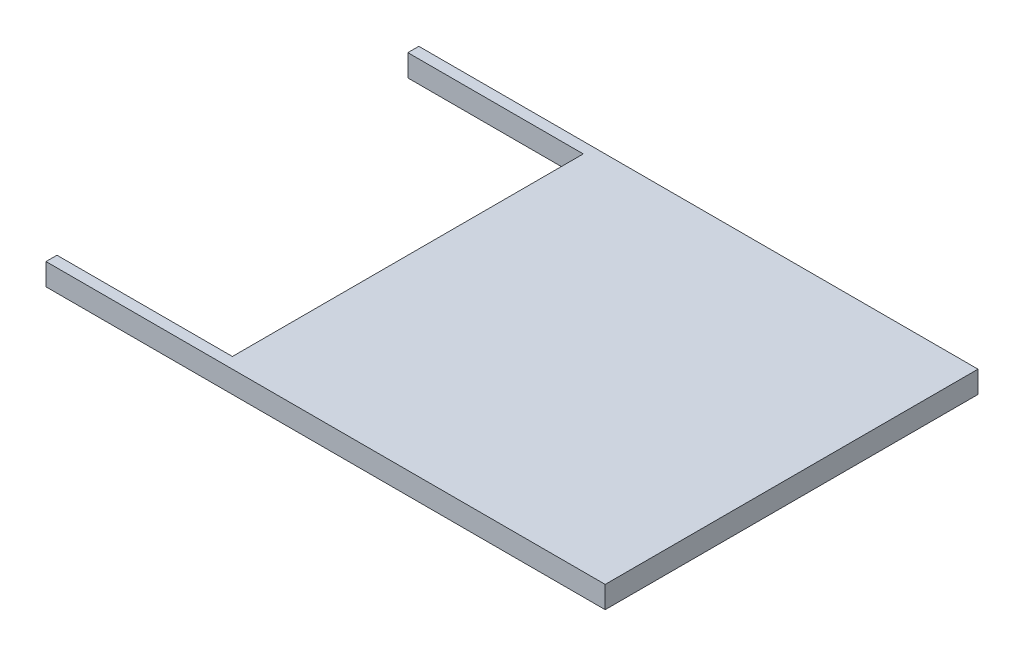
SolidWorks part; units mm, degrees
ref_plane "Front Plane" through (0, 0, 0) normal (0, 0, 1) x (1, 0, 0)
ref_plane "Top Plane" through (0, 0, 0) normal (0, 1, 0) x (1, 0, 0)
ref_plane "Right Plane" through (0, 0, 0) normal (1, 0, 0) x (0, 0, -1)
sketch "Sketch1" plane through (0, 0, 0) normal (0, 1, 0) x (1, 0, 0)
  line L0 (-55, 0) -> (55, 0) construction
  line L1 (-128.9215, -53.975) -> (128.9215, -53.975)
  line L2 (-128.9215, -53.975) -> (-128.9215, 53.975)
  line L3 (-128.9215, 53.975) -> (128.9215, 53.975)
  line L4 (128.9215, -53.975) -> (128.9215, 53.975)
  line L5 (-128.9215, -53.975) -> (128.9215, 53.975) construction
  line L6 (-128.9215, 53.975) -> (128.9215, -53.975) construction
  line L7 (-128.9215, 53.975) -> (-122.5715, 53.975)
  line L8 (-128.9215, 53.975) -> (-128.9215, 45.339)
  line L9 (-128.9215, 45.339) -> (-122.5715, 45.339)
  line L10 (-122.5715, 53.975) -> (-122.5715, 45.339)
  line L11 (-122.5715, 53.975) -> (-100.0925, 53.975)
  line L12 (-122.5715, 53.975) -> (-122.5715, 45.339)
  line L13 (-122.5715, 45.339) -> (-100.0925, 45.339)
  line L14 (-100.0925, 53.975) -> (-100.0925, 45.339)
  line L15 (-100.0925, 53.975) -> (-93.7425, 53.975)
  line L16 (-100.0925, 53.975) -> (-100.0925, 45.339)
  line L17 (-100.0925, 45.339) -> (-93.7425, 45.339)
  line L18 (-93.7425, 53.975) -> (-93.7425, 45.339)
  line L19 (-122.5715, -45.339) -> (-100.0925, -45.339)
  line L20 (-128.9215, -45.339) -> (-122.5715, -45.339)
  line L21 (-122.5715, -53.975) -> (-122.5715, -45.339)
  line L22 (-100.0925, -53.975) -> (-100.0925, -45.339)
  line L23 (-100.0925, -45.339) -> (-93.7425, -45.339)
  line L24 (-93.7425, -53.975) -> (-93.7425, -45.339)
  line L25 (-125.7465, -45.339) -> (-125.7465, 45.339)
  line L27 (-93.7425, -45.339) -> (-96.9175, -45.339)
  line L28 (-93.7425, -45.339) -> (-93.7425, 45.339)
  line L29 (-93.7425, 45.339) -> (-96.9175, 45.339)
  line L30 (-96.9175, -45.339) -> (-96.9175, 45.339)
  point P0 (0, 0)
  point P13 (-125.7465, 45.339)
  point P18 (-125.7465, -45.339)
  dimension "D1" = 22.479
  dimension "D2" = 6.35
  dimension "D3" = 6.35
  dimension "D4" = 8.636
  dimension "D5" = 107.95
  dimension "D6" = 3.175
extrude "Boss-Extrude1" add sketch "Sketch1" against normal blind 6.35 contours L24 L1 L4 L3 L18 L17 L13 L9 L2 L20 L19 L23 | L1 L21 L20 L2 | L1 L24 L23 L22 | L10 L3 L2 L9 | L14 L3 L10 L13 | L18 L3 L14 L17 | L1 L22 L19 L21 | L2 L1 L4 L3 region at (-125.7465, 0, 49.657) region at (-111.332, 0, 49.657) region at (-96.9175, 0, 49.657) region at (-125.7465, 0, -49.657) region at (17.5895, 0, 0) region at (-111.332, 0, -49.657) region at (-96.9175, 0, -49.657)
extrude "Boss-Extrude2" add sketch "Sketch1<3>" along normal blind 19.05 contours L10 L3 L2 L9 | L18 L3 L14 L17 | L1 L24 L23 L22 | L1 L21 L20 L2 | L20 L25 L9 L2 | L30 L23 L28 L17 region at (-125.7465, 0, 49.657) region at (-127.334, 0, 0) region at (-96.9175, 0, 49.657) region at (-125.7465, 0, -49.657) region at (-95.33, 0, 0) region at (-96.9175, 0, -49.657)
sketch "Sketch1<3>" plane through (0, 0, 0) normal (0, 1, 0) x (1, 0, 0) same geometry as "Sketch1"
sketch "Sketch3" plane through (0, 0, 53.975) normal (0, 0, 1) x (1, 0, 0)
  line L1 (-122.5715, 0) -> (-100.0925, 0) construction
  circle A0 centre (-111.332, -1.651) radius 0.762
  dimension "D1" = 1.524
  dimension "D2" = 11.2395
  dimension "D3" = 1.651
extrude "Cut-Extrude1" cut sketch "Sketch3" against normal blind 6.35
mirror "Mirror1" about plane through (0, 0, 0) normal (0, 0, 1) of "Cut-Extrude1"
sketch "Sketch4" plane through (0, 0, 0) normal (0, 1, 0) x (1, 0, 0)
  line L1 (-83.8035, 50.8) -> (17.7965, 50.8)
  line L2 (-83.8035, 50.8) -> (-83.8035, -50.8)
  line L3 (-83.8035, -50.8) -> (17.7965, -50.8)
  line L4 (17.7965, 50.8) -> (17.7965, -50.8)
  line L5 (128.9215, -53.975) -> (128.9215, 53.975) construction
  line L6 (20.9715, 50.8) -> (122.5715, 50.8)
  line L7 (20.9715, 50.8) -> (20.9715, -50.8)
  line L8 (20.9715, -50.8) -> (122.5715, -50.8)
  line L9 (122.5715, 50.8) -> (122.5715, -50.8)
  line L11 (-93.7425, 53.975) -> (128.9215, 53.975) construction
  dimension "D1" = 101.6
  dimension "D2" = 101.6
  dimension "D3" = 101.6
  dimension "D4" = 101.6
  dimension "D5" = 6.35
  dimension "D6" = 3.175
  dimension "D7" = 3.175
  dimension "D8" = 3.175
extrude "Cut-Extrude2" cut sketch "Sketch4" against normal blind 6.35 contours L4 L1 L2 L3 region at (-33.0035, 0, 0)
sketch "Sketch5" plane through (0, 0, 0) normal (0, 1, 0) x (1, 0, 0)
  line L0 (-34.0981, 50.8) -> (-33.0035, -50.8)
  line L1 (-83.8035, 50.8) -> (17.7965, 50.8) construction
  line L2 (-83.8035, -50.8) -> (17.7965, -50.8) construction
  line L3 (-33.0035, -50.8) -> (-33.0035, -55.4285)
  line L4 (-34.0926, 50.2924) -> (-34.0926, 53.975)
  line L5 (-93.7425, 53.975) -> (128.9215, 53.975) construction
  line L7 (-33.0035, -55.4285) -> (-163.948, -55.4285)
  line L8 (-33.0035, -55.4285) -> (-33.0035, 91.4988)
  line L9 (-33.0035, 91.4988) -> (-163.948, 91.4988)
  line L10 (-163.948, -55.4285) -> (-163.948, 91.4988)
extrude "Cut-Extrude3" cut sketch "Sketch5" against normal blind 45.974 and the other way blind 35.56 contours L10 L7 L3 L8 L9 region at (-98.4757, 0, -18.0352)
